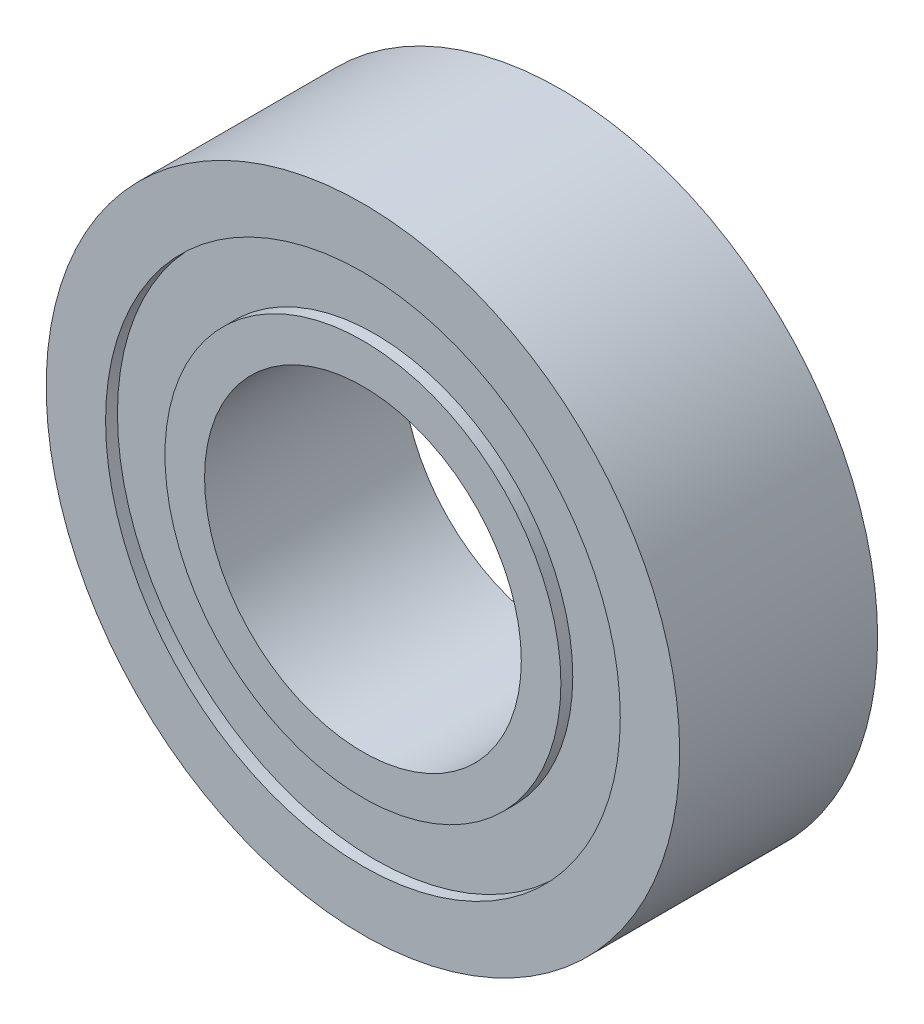
SolidWorks part; units mm, degrees
material "AISI 316 Annealed Stainless Steel Bar (SS)"
ref_plane "Front Plane" through (0, 0, 0) normal (0, 0, 1) x (1, 0, 0)
ref_plane "Top Plane" through (0, 0, 0) normal (0, 1, 0) x (1, 0, 0)
ref_plane "Right Plane" through (0, 0, 0) normal (1, 0, 0) x (0, 0, -1)
sketch "Sketch1" plane through (0, 0, 0) normal (0, 0, 1) x (1, 0, 0)
  circle A0 centre (0, 0) radius 8
  dimension "D1" = 16
extrude "Body" add sketch "Sketch1" against normal blind 2.5 and the other way blind 2.5
sketch "Sketch3" plane through (0, 0, 2.5) normal (0, 0, 1) x (1, 0, 0)
  circle A0 centre (0, 0) radius 4
  dimension "D1" = 8
extrude "Bore-Hole" cut sketch "Sketch3" against normal through all
sketch "Sketch4" plane through (0, 0, 2.5) normal (0, 0, 1) x (1, 0, 0)
  line L0 (5, 0) -> (6.5, 0) construction
  circle A0 centre (0, 0) radius 5
  circle A1 centre (0, 0) radius 6.5
  circle A3 centre (0, 0) radius 8 construction
  dimension "D1" = 10
  dimension "D2" = 1.5
extrude "Decoration" cut sketch "Sketch4" against normal blind 0.3
mirror "Mirror1" about plane through (0, 0, 0) normal (0, 0, 1) of "Decoration"
